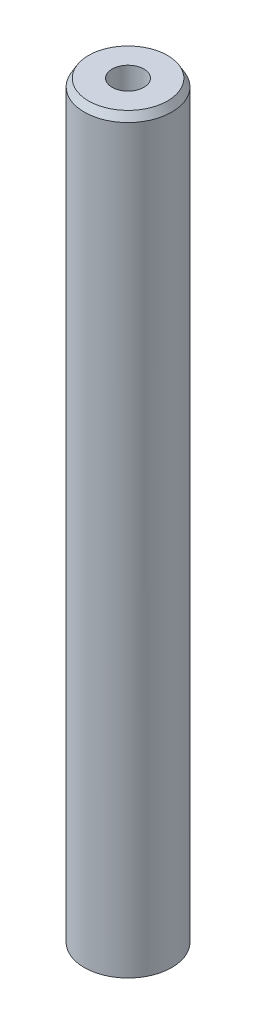
SolidWorks part; units mm, degrees
ref_plane "Front Plane" through (0, 0, 0) normal (0, 0, 1) x (1, 0, 0)
ref_plane "Top Plane" through (0, 0, 0) normal (0, 1, 0) x (1, 0, 0)
ref_plane "Right Plane" through (0, 0, 0) normal (1, 0, 0) x (0, 0, -1)
sketch "Sketch1" plane through (0, 0, 0) normal (0, 1, 0) x (1, 0, 0)
  circle A0 centre (0, 0) radius 12.5
  dimension "SHAFT_OD" = 25
extrude "Boss-Extrude1" add sketch "Sketch1" along normal blind 214.8137
sketch "Sketch2" plane through (0, 0, 0) normal (0, 1, 0) x (1, 0, 0)
  circle A0 centre (0, 0) radius 4.5353
  dimension "BORE_D" = 9.0706
extrude "Cut-Extrude1" cut sketch "Sketch2" along normal through all
chamfer "Chamfer1" distance 2.1367 angle 30 2 edges at (0, 214.8137, 12.5) (0, 0, 12.5) first distance on face at (0, 214.8137, 12.5) first distance on face at (0, 0, 4.5353)
